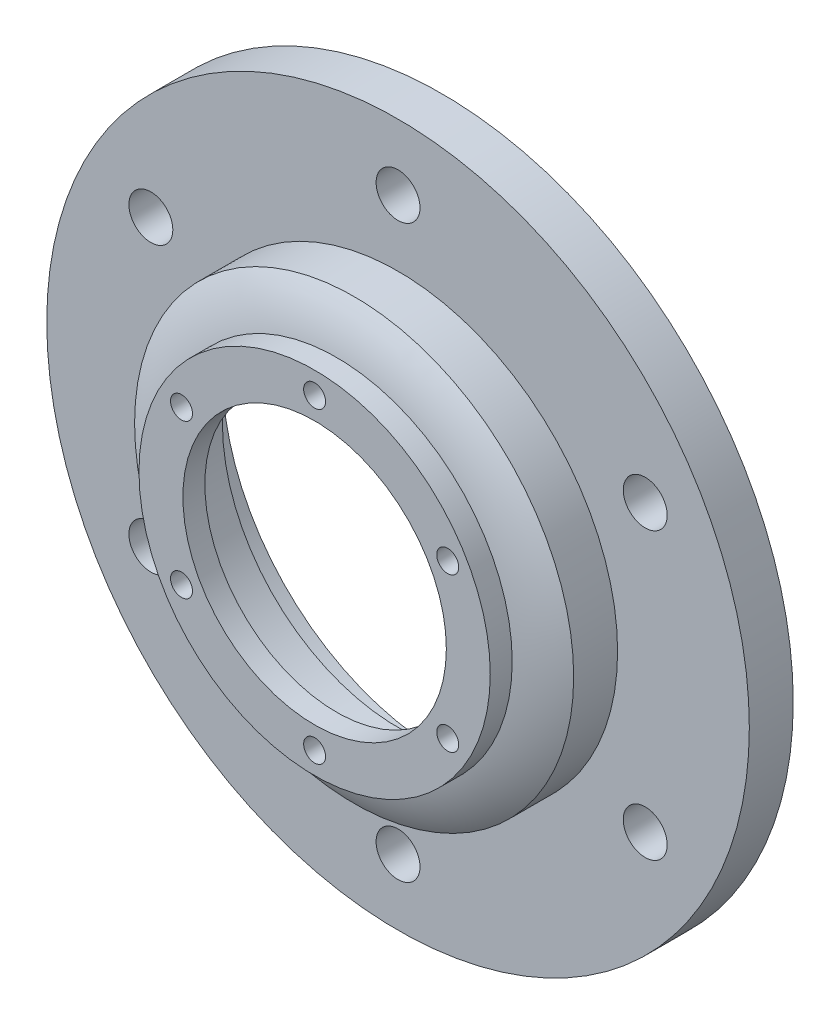
SolidWorks part; units mm, degrees
ref_plane "Front Plane" through (0, 0, 0) normal (0, 0, 1) x (1, 0, 0)
ref_plane "Top Plane" through (0, 0, 0) normal (0, 1, 0) x (1, 0, 0)
ref_plane "Right Plane" through (0, 0, 0) normal (1, 0, 0) x (0, 0, -1)
sketch "Sketch1" plane through (0, 0, 0) normal (0, 0, 1) x (1, 0, 0)
  circle A0 centre (0, 0) radius 50
extrude "Extrude-Thin1" add sketch "Sketch1" along normal blind 10 thin thin type one direction wall 30
sketch "Sketch2" plane through (0, 0, 10) normal (0, 0, 1) x (1, 0, 0)
  circle A2 centre (0, 65) radius 5
  circle A3 centre (56.2917, 32.5) radius 5
  circle A4 centre (56.2917, -32.5) radius 5
  circle A5 centre (0, -65) radius 5
  circle A6 centre (-56.2917, -32.5) radius 5
  circle A7 centre (-56.2917, 32.5) radius 5
  point P15 (0, 0)
  dimension "D1" = 6
extrude "Cut-Extrude1" cut sketch "Sketch2" against normal through all
sketch "Sketch3" plane through (0, 0, 10) normal (0, 0, 1) x (1, 0, 0)
  circle A0 centre (0, 0) radius 40
extrude "Extrude-Thin2" add sketch "Sketch3" along normal blind 10 separate body thin contours A0 thin type one direction wall 10
sketch "Sketch4" plane through (0, 0, 0) normal (1, 0, 0) x (0, 0, -1)
  line L0 (-20, 40) -> (-24, 40)
  line L1 (-20, 50) -> (-20, -50) construction
  line L2 (-20, 40) -> (-20, -40) construction
  line L3 (0, 0) -> (-94.1976, 0)
  line L4 (-20, 50) -> (-20, 40)
  spline S0 degree 2 poles (-20, 50) (-22.9365, 45.3816) (-24, 40) knots 0 0 0 1 1 1
  dimension "D1" = 4
revolve "Revolve1" add sketch "Sketch4" angle 360 about L3 region at (0, 43.6011, 21.4645)
ref_plane "Plane1" through (0, 0, 24) normal (0, 0, 1) x (1, 0, 0)
sketch "Sketch7" plane through (0, 0, 24) normal (0, 0, 1) x (1, 0, 0)
  circle A0 centre (0, 0) radius 30
extrude "Extrude-Thin3" add sketch "Sketch7" along normal blind 5 separate body thin contours A0 thin type one direction wall 10
sketch "Sketch8" plane through (0, 0, 29) normal (0, 0, 1) x (1, 0, 0)
  line L0 (0, 30) -> (0, 40)
  circle A0 centre (0, 0) radius 30 construction
  circle A1 centre (0, 0) radius 40 construction
  circle A2 centre (0, 35) radius 2.5
  circle A3 centre (30.3109, 17.5) radius 2.5
  circle A4 centre (30.3109, -17.5) radius 2.5
  circle A5 centre (0, -35) radius 2.5
  circle A6 centre (-30.3109, -17.5) radius 2.5
  circle A7 centre (-30.3109, 17.5) radius 2.5
  point P21 (0, 0)
  dimension "D1" = 6
extrude "Cut-Extrude2" cut sketch "Sketch8" against normal through all contours A7 | L0 A2 | L0 A2 | A3 | A4 | A5 | A6 region at (-1.061, 35, 29) region at (1.061, 35, 29) region at (30.3109, 17.5, 29) region at (30.3109, -17.5, 29) region at (0, -35, 29) region at (-30.3109, -17.5, 29) region at (-30.3109, 17.5, 29)
